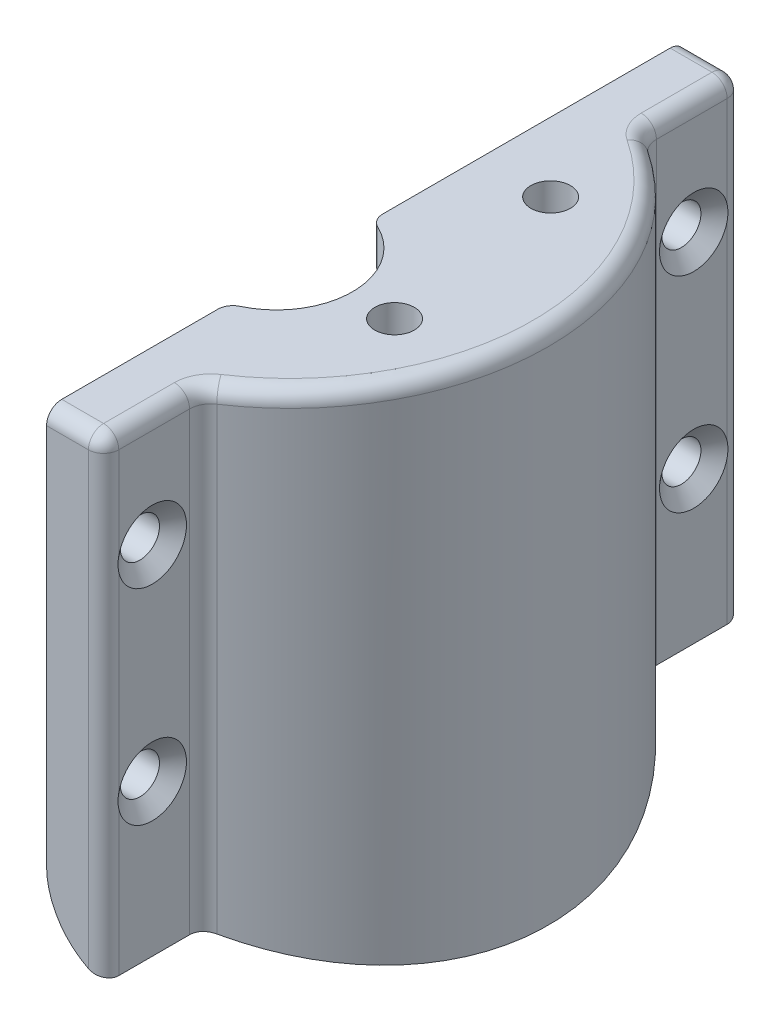
SolidWorks part; units mm, degrees
ref_plane "Front Plane" through (0, 0, 0) normal (0, 0, 1) x (1, 0, 0)
ref_plane "Top Plane" through (0, 0, 0) normal (0, 1, 0) x (1, 0, 0)
ref_plane "Right Plane" through (0, 0, 0) normal (1, 0, 0) x (0, 0, -1)
sketch "Sketch1" plane through (0, 0, 0) normal (0, 1, 0) x (1, 0, 0)
  line L0 (0, 0) -> (12.192, 0) construction
  line L1 (12.192, 26.67) -> (12.192, 0.5451)
  line L2 (12.192, 26.67) -> (16.9545, 26.67)
  line L4 (12.192, -26.67) -> (16.9545, -26.67)
  line L6 (10.2061, -5.4864) -> (5.842, 0) construction
  line L7 (5.842, 0) -> (5.842, -0.8737) construction
  line L8 (12.192, -11.5179) -> (12.192, -26.67)
  line L9 (5.842, -10.0991) -> (5.842, -18.3583) construction
  line L10 (16.9545, 26.67) -> (16.9545, 19.9773)
  line L11 (16.9545, -26.67) -> (16.9545, -19.9773)
  line L12 (16.9545, 19.9773) -> (16.9545, 18.5105)
  line L13 (16.9545, -19.9773) -> (16.9545, -18.5105)
  circle A0 centre (5.842, 0) radius 15.494 construction
  arc A3 (12.192, -11.5179) -> (12.192, 0.5451) centre (10.2061, -5.4864) ccw
  arc A6 (16.9545, -18.5105) -> (16.9545, 18.5105) centre (5.842, 0) ccw
  point P6 (12.192, 0)
  dimension "D4" = 30.988
  dimension "D8" = 43.18
  dimension "D1" = 12.192
  dimension "D2" = 53.34
  dimension "D3" = 5.842
  dimension "D6" = 4.7625
  dimension "D7" = 4.7625
  dimension "D9" = 7.0104
  dimension "D10" = 38.5
extrude "Boss-Extrude1" add sketch "Sketch1" against normal blind 43.942
sketch "Sketch3" plane through (0, -43.942, 0) normal (0, -1, 0) x (1, 0, 0)
  line L6 (12.192, 26.67) -> (12.192, 11.5179)
  line L7 (12.192, -0.5451) -> (12.192, -26.67)
  line L8 (12.192, -26.67) -> (16.9545, -26.67)
  line L9 (16.9545, -26.67) -> (16.9545, -18.5105)
  line L10 (16.9545, 18.5105) -> (16.9545, 26.67)
  line L11 (16.9545, 26.67) -> (12.192, 26.67)
  line L12 (12.192, 17.0161) -> (12.192, 11.5179)
  line L13 (12.192, -0.5451) -> (12.192, -17.0161)
  circle A0 centre (5.842, 0) radius 15.494 construction
  arc A2 (12.192, -0.5451) -> (12.192, 11.5179) centre (10.2061, 5.4864) ccw
  arc A3 (16.9545, -18.5105) -> (16.9545, 18.5105) centre (5.842, 0) ccw
  arc A4 (12.192, -0.5451) -> (12.192, 11.5179) centre (10.2061, 5.4864) ccw
  arc A7 (12.192, -17.0161) -> (12.192, 17.0161) centre (4.826, 0) ccw
  arc A10 (16.9545, -18.5105) -> (16.9545, 18.5105) centre (5.842, 0) ccw
  point P14 (0, 0)
  point P16 (0, 0)
  line M11 (12.192, 26.67) -> (12.192, 11.5179)
  arc M12 (12.192, 11.5179) -> (12.192, -0.5451) centre (10.2061, 5.4864) cw
  line M13 (12.192, -0.5451) -> (12.192, -26.67)
  dimension "D2" = 37.084
  dimension "D3" = 1.016
  dimension "D1" = 0
extrude "Cut-Extrude1" cut sketch "Sketch3" against normal blind 40.767 contours A7 M13 M11 M12 region at (17.2605, -43.942, -0.8969)
fillet "Fillet1" radius 1.27 2 edges at (12.192, -1.5875, -0.5451) (12.192, -1.5875, 11.5179)
sketch "Sketch4" plane through (16.9545, 0, 0) normal (1, 0, 0) x (0, 0, -1)
  line L0 (-22.606, 0) -> (-22.606, -39.1703) construction
  line L1 (-26.67, 0) -> (-18.5105, 0) construction
  line L2 (-26.67, -43.942) -> (-26.67, 0) construction
  point P6 (-22.606, -9.525)
  point P7 (-22.606, -26.6446)
  dimension "D1" = 4.064
  dimension "D2" = 9.525
  dimension "D3" = 17.1196
hole_wizard "CSK for #4 Flat Head Machine Screw (100)1" positions "Sketch5" profile "Sketch6" countersink size "#4" standard "ANSI Inch"
sketch "Sketch5" plane through (16.9545, 0, 0) normal (1, 0, 0) x (0, 0, -1)
  point P0 (-22.606, -9.525)
  point P3 (-22.606, -26.6446)
sketch "Sketch6" plane through (16.9545, -9.525, 22.606) normal (0, 1, 0) x (0, 0, -1)
  line L0 (0, 0) -> (0, 7.8386)
  line L1 (0, 7.8386) -> (1.6319, 6.858)
  line L2 (1.6319, 6.858) -> (1.6319, 1.0284)
  line L3 (1.6319, 1.0284) -> (2.8575, 0)
  line L5 (2.8575, 0) -> (0, 0)
  line L6 (-1.6319, 1.0284) -> (-2.8575, 0) construction
  line L10 (0, 7.8386) -> (-1.632, 6.858) construction
  line L11 (0, -6.35) -> (0, 107.95) construction
  dimension "Hole Dia." = 3.2639
  dimension "Hole Depth" = 6.858
  dimension "Near C'Sink Dia." = 5.715
  dimension "Near C'Sink Angle" = 100
  dimension "Drill Angle" = 118
mirror "Mirror1" about plane through (0, 0, 0) normal (0, 0, 1) of "CSK for #4 Flat Head Machine Screw (100)1"
sketch "Sketch7" plane through (0, 0, 26.67) normal (0, 0, 1) x (1, 0, 0)
  line L0 (12.192, -37.5631) -> (29.718, -43.942)
  line L1 (12.192, -43.942) -> (12.192, 0) construction
  line L2 (12.192, -37.5631) -> (12.192, -43.942)
  line L3 (12.192, -43.942) -> (29.718, -43.942)
  dimension "D1" = 110
  dimension "D2" = 17.526
extrude "Cut-Extrude2" cut sketch "Sketch7" against normal through all
fillet "Fillet3" radius 1.778 2 edges at (16.9545, -19.6482, -18.5105) (16.9545, -19.6482, 18.5105)
fillet "Fillet4" radius 1.27 9 edges at (16.9545, 0, 23.0805) (17.1664, 0, 18.6491) (16.9545, 0, -23.0805) (17.1664, 0, -18.6491) (16.9545, -19.6482, 26.67) (16.9545, -19.6482, -26.67) (14.5732, 0, -26.67) (14.5733, 0, 26.67) (27.432, 0, 0)
fillet "Fillet5" radius 6.35 2 edges at (12.192, -37.5631, -21.8431) (12.192, -37.5631, 21.8431)
sketch "Sketch8" plane through (0, 0, 0) normal (0, 1, 0) x (1, 0, 0)
  line L0 (5.842, 0) -> (5.842, 15.494) construction
  line L1 (17.9677, 9.6452) -> (5.842, 0) construction
  line L2 (5.842, 0) -> (3.5518, 15.3238) construction
  circle A0 centre (5.842, 0) radius 15.494 construction
  circle A1 centre (5.842, 0) radius 15.494 construction
  circle A2 centre (17.9677, 9.6452) radius 1.651
  circle A3 centre (20.2579, -5.6786) radius 1.651
  point P11 (5.842, 0)
  dimension "D1" = 3.302
  dimension "D2" = 8.5
  dimension "D3" = 60
  dimension "D4" = 2
extrude "Cut-Extrude3" cut sketch "Sketch8" against normal blind 40.767
